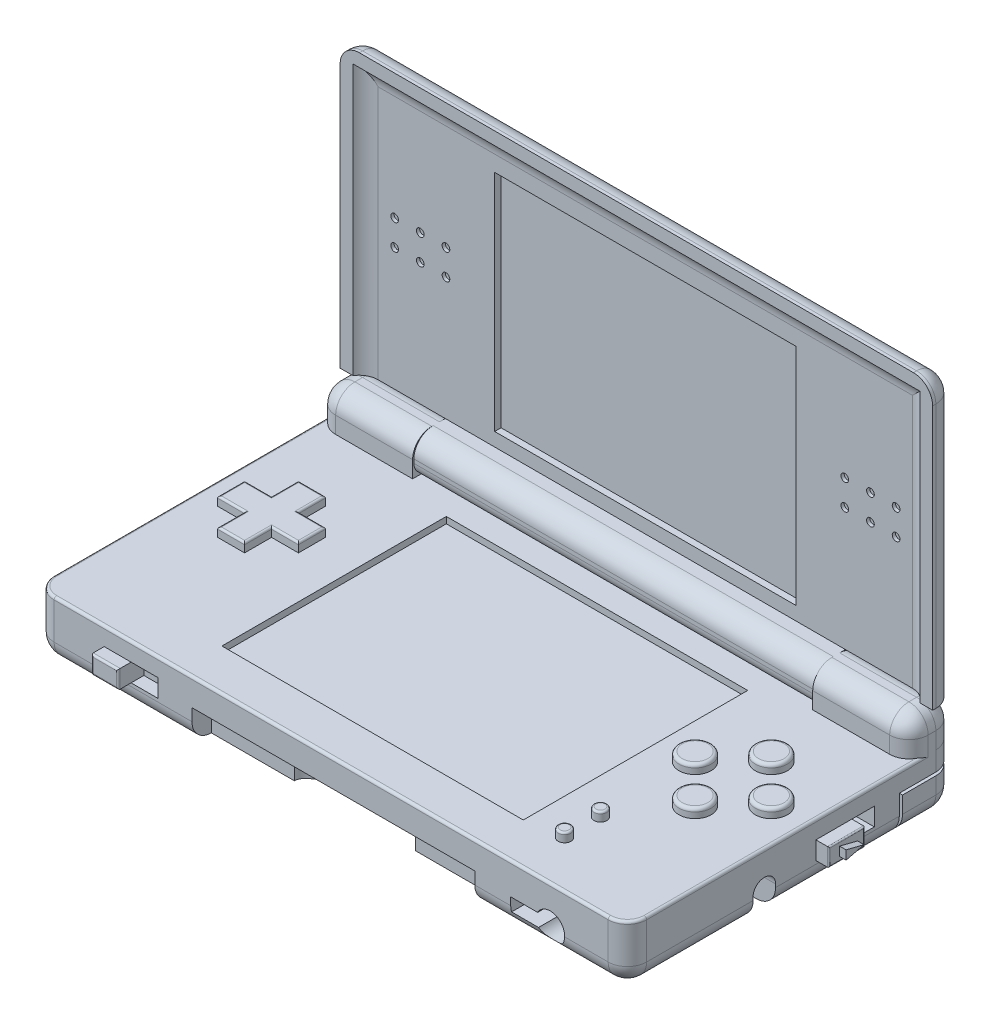
SolidWorks part; units mm, degrees
ref_plane "정면" through (0, 0, 0) normal (0, 0, 1) x (1, 0, 0)
ref_plane "윗면" through (0, 0, 0) normal (0, 1, 0) x (1, 0, 0)
ref_plane "우측면" through (0, 0, 0) normal (1, 0, 0) x (0, 0, -1)
sketch "스케치1" plane through (0, 0, 0) normal (0, 1, 0) x (1, 0, 0)
  line L0 (-46.2, 25.55) -> (46.2, -25.55) construction
  line L1 (-46.2, 25.55) -> (46.2, 25.55)
  line L2 (-46.2, 25.55) -> (-46.2, -25.55)
  line L3 (-46.2, -25.55) -> (46.2, -25.55)
  line L4 (46.2, 25.55) -> (46.2, -25.55)
  line L5 (46.2, 25.55) -> (-46.2, -25.55) construction
  dimension "D1" = 92.4
  dimension "D2" = 51.1
extrude "보스-돌출1" add sketch "스케치1" along normal blind 9.1 contours L1 L4 L3 L2
fillet "필렛1" radius 3 3 edges at (-46.2, 0, 0) (0, 0, 25.55) (-46.2, 4.55, 25.55)
fillet "필렛2" radius 3 3 edges at (46.2, 0, -1.5) (46.2, 0.8787, 24.6713) (46.2, 6.05, 25.55)
fillet "필렛3" radius 3 5 edges at (-46.2, 6.05, -25.55) (-45.3213, 0.8787, -25.55) (0, 0, -25.55) (45.3213, 0.8787, -25.55) (46.2, 6.05, -25.55)
sketch "스케치4" plane through (0, 9.1, 0) normal (0, 1, 0) x (1, 0, 0)
  line L0 (-43.2, 25.55) -> (43.2, 25.55) construction
  line L1 (31.2, 25.55) -> (46.2, 25.55)
  line L2 (31.2, 25.55) -> (31.2, 18.35)
  line L3 (31.2, 18.35) -> (46.2, 18.35)
  line L4 (46.2, 25.55) -> (46.2, 18.35)
  line L5 (46.2, 22.55) -> (46.2, -22.55) construction
  line L6 (-46.2, 22.55) -> (-46.2, -22.55) construction
  line L7 (-46.2, 25.55) -> (-31.2, 25.55)
  line L8 (-46.2, 25.55) -> (-46.2, 18.35)
  line L9 (-46.2, 18.35) -> (-31.2, 18.35)
  line L10 (-31.2, 25.55) -> (-31.2, 18.35)
  dimension "D1" = 7.2
  dimension "D2" = 15
  dimension "D3" = 7.2
  dimension "D4" = 15
extrude "보스-돌출4" add sketch "스케치4" along normal blind 5.6 contours L9 L10 L7 L8 | L3 L4 L1 L2
fillet "필렛11" radius 3 6 edges at (46.2, 14.7, -21.95) (46.2, 11.9, -25.55) (38.7, 14.7, -25.55) (-46.2, 14.7, -21.95) (-38.7, 14.7, -25.55) (-46.2, 11.9, -25.55)
fillet "필렛13" radius 3 3 edges at (-45.3213, 13.8213, -18.35) (-37.2, 14.7, -18.35)
fillet "필렛14" radius 3 3 edges at (46.2, 10.4, -18.35) (45.3213, 13.8213, -18.35) (37.2, 14.7, -18.35)
sketch "스케치10" plane through (0, 9.1, 0) normal (0, 1, 0) x (1, 0, 0)
  line L0 (-31.2, 25.55) -> (31.2, 25.55) construction
  line L1 (-31.2, 25.55) -> (31.2, 25.55)
  line L2 (-31.2, 25.55) -> (-31.2, 18.55)
  line L3 (-31.2, 18.55) -> (31.2, 18.55)
  line L4 (31.2, 25.55) -> (31.2, 18.55)
  dimension "D1" = 7
extrude "보스-돌출12" add sketch "스케치10" along normal blind 5.6 separate body contours L3 L4 L1 L2
fillet "필렛17" radius 2 1 edges at (0, 9.1, -25.55)
fillet "필렛18" radius 2 1 edges at (0, 9.1, -18.55)
fillet "필렛20" radius 3 1 edges at (0, 14.7, -18.55)
sketch "스케치12" plane through (0, 14.7, 0) normal (0, 1, 0) x (1, 0, 0)
  line L0 (-31.2, 25.55) -> (31.2, 25.55) construction
  line L1 (-46.2, 25.55) -> (46.2, 25.55)
  line L2 (-46.2, 25.55) -> (-46.2, 22.05)
  line L3 (-46.2, 22.05) -> (46.2, 22.05)
  line L4 (46.2, 25.55) -> (46.2, 22.05)
  line L5 (-46.2, 21.35) -> (-46.2, -22.55) construction
  dimension "D1" = 92.4
  dimension "D2" = 3.5
  dimension "D3" = 0
extrude "보스-돌출13" add sketch "스케치12" along normal blind 44.1
sketch "스케치13" plane through (0, 0, -22.05) normal (0, 0, 1) x (1, 0, 0)
  line L0 (-46.2, 58.8) -> (-46.2, 14.7) construction
  line L1 (-44.2, 56.8) -> (44.2, 56.8)
  line L2 (-44.2, 56.8) -> (-44.2, 14.7)
  line L3 (-44.2, 14.7) -> (44.2, 14.7)
  line L4 (44.2, 56.8) -> (44.2, 14.7)
  line L7 (-43.2, 14.7) -> (43.2, 14.7) construction
  line L9 (-46.2, 58.8) -> (46.2, 58.8) construction
  line L10 (46.2, 58.8) -> (46.2, 14.7) construction
  dimension "D1" = 2
  dimension "D2" = 2
  dimension "D3" = 2
  dimension "D4" = 0
extrude "컷-돌출3" cut sketch "스케치13" against normal blind 1.4
fillet "필렛26" radius 3 3 edges at (-44.2, 35.75, -23.45) (0, 56.8, -23.45) (44.2, 35.75, -23.45)
fillet "필렛27" radius 3 1 edges at (46.2, 58.8, -23.8)
fillet "필렛28" radius 3 1 edges at (-46.2, 58.8, -23.8)
fillet "필렛29" radius 3 5 edges at (45.3213, 57.9213, -25.55) (-46.2, 35.25, -25.55) (-45.3213, 57.9213, -25.55) (46.2, 35.25, -25.55) (0, 58.8, -25.55)
sketch "스케치14" plane through (0, 9.1, 0) normal (0, 1, 0) x (1, 0, 0)
  line L0 (-43.2, 18.35) -> (-31.2, 18.35) construction
  line L1 (-38.5, 7.85) -> (-38.5, 3.65)
  line L2 (-42.7, 3.65) -> (-42.7, -0.55)
  line L3 (-42.7, -0.55) -> (-38.5, -0.55)
  line L4 (-38.5, -0.55) -> (-38.5, -4.75)
  line L5 (-46.2, 21.35) -> (-46.2, -22.55) construction
  line L7 (-38.5, -4.75) -> (-34.3, -4.75)
  line L8 (-34.3, -4.75) -> (-34.3, -0.55)
  line L9 (-34.3, -0.55) -> (-30.1, -0.55)
  line L10 (-30.1, -0.55) -> (-30.1, 3.65)
  line L11 (-30.1, 3.65) -> (-34.3, 3.65)
  line L12 (-34.3, 3.65) -> (-34.3, 7.85)
  line L13 (-34.3, 7.85) -> (-38.5, 7.85)
  line L14 (-38.5, 3.65) -> (-42.7, 3.65)
  dimension "D1" = 4.2
  dimension "D2" = 4.2
  dimension "D3" = 4.2
  dimension "D4" = 4.2
  dimension "D5" = 10.5
  dimension "D6" = 3.5
  dimension "D7" = 4.2
  dimension "D8" = 4.2
extrude "보스-돌출14" add sketch "스케치14" along normal blind 1.4
sketch "스케치15" plane through (0, 9.1, 0) normal (0, 1, 0) x (1, 0, 0)
  line L0 (29, 2.2) -> (40.9, 2.2) construction
  line L1 (34.95, 8.15) -> (34.95, -3.75) construction
  line L2 (46.2, 21.35) -> (46.2, -22.55) construction
  line L3 (31.2, 18.35) -> (43.2, 18.35) construction
  circle A0 centre (34.95, 8.15) radius 2.5
  circle A1 centre (29, 2.2) radius 2.5
  circle A2 centre (34.95, -3.75) radius 2.5
  circle A3 centre (40.9, 2.2) radius 2.5
  point P8 (34.95, 2.2)
  point P9 (34.95, 2.2)
  point P10 (34.95, 10.65)
  point P13 (43.4, 2.2)
  dimension "D1" = 5
  dimension "D5" = 11.9
  dimension "D6" = 11.9
  dimension "D7" = 7.7
  dimension "D2" = 5
  dimension "D3" = 5
  dimension "D4" = 5
  dimension "D8" = 2.8
extrude "보스-돌출15" add sketch "스케치15" along normal blind 1.4 contours A0 | A1 | A3 | A2
sketch "스케치16" plane through (0, 9.1, 0) normal (0, 1, 0) x (1, 0, 0)
  line L0 (-43.2, -25.55) -> (43.2, -25.55) construction
  line L1 (46.2, 21.35) -> (46.2, -22.55) construction
  circle A0 centre (29.1, -12.65) radius 1
  circle A1 centre (29.1, -18.25) radius 1
  point P4 (29.1, -19.25)
  point P7 (30.1, -18.25)
  dimension "D1" = 2
  dimension "D5" = 2
  dimension "D2" = 6.3
  dimension "D3" = 16.1
  dimension "D4" = 5.6
extrude "보스-돌출16" add sketch "스케치16" along normal blind 1.4
sketch "스케치17" plane through (0, 0, -23.45) normal (0, 0, 1) x (1, 0, 0)
  line L0 (-46.2, 55.8) -> (-46.2, 14.7) construction
  line L5 (41.6623, 54.2623) -> (-41.6623, 54.2623) construction
  line L6 (0, 68.9396) -> (0, -17.3507) construction
  circle A0 centre (39.1, 33.8515) radius 0.6
  circle A1 centre (35.1, 33.8515) radius 0.6
  circle A2 centre (31.1, 33.8515) radius 0.6
  circle A3 centre (31.1, 37.8515) radius 0.6
  circle A4 centre (35.1, 37.8515) radius 0.6
  circle A5 centre (39.1, 37.8515) radius 0.6
  circle A7 centre (-39.1, 33.8515) radius 0.6
  circle A8 centre (-35.1, 33.8515) radius 0.6
  circle A9 centre (-31.1, 33.8515) radius 0.6
  circle A10 centre (-39.1, 37.8515) radius 0.6
  circle A11 centre (-35.1, 37.8515) radius 0.6
  circle A12 centre (-31.1, 37.8515) radius 0.6
  point P0 (-38.5, 37.8515)
  point P27 (-35.7, 37.8515)
  point P28 (-34.5, 37.8515)
  point P29 (-31.7, 37.8515)
  point P30 (-31.1, 34.4515)
  point P31 (-31.1, 37.2515)
  point P32 (-35.1, 37.2515)
  point P33 (-35.1, 34.4515)
  point P34 (-34.5, 33.8515)
  point P35 (-35.7, 33.8515)
  point P36 (-38.5, 33.8515)
  point P37 (-31.7, 33.8515)
  point P38 (-39.1, 34.4515)
  dimension "D1" = 7.7
  dimension "D5" = 1.2
  dimension "D6" = 16.4108
  dimension "D2" = 2.8
  dimension "D3" = 2.8
  dimension "D4" = 2.8
  dimension "D11" = 2.8
  dimension "D12" = 2.8
extrude "컷-돌출4" cut sketch "스케치17" against normal blind 0.5 contours A10 | A11 | A12 | A8 | A7 | A9 | A3 | A2 | A1 | A0 | A5 | A4
sketch "스케치20" plane through (0, 0, -25.55) normal (0, 0, -1) x (-1, 0, 0)
  line L1 (43.2, 0) -> (-43.2, 0) construction
  line L2 (-22.4, 4.9) -> (-20.3, 4.9)
  line L3 (-22.4, 4.9) -> (-22.4, 3.5)
  line L4 (-22.4, 3.5) -> (-20.3, 3.5)
  line L6 (-20.3, 4.9) -> (-20.3, 3.5)
  line L7 (-46.2, 3) -> (-46.2, 9.1) construction
  line L8 (-18.2, 4.9) -> (-16.1, 4.9)
  line L9 (-18.2, 4.9) -> (-18.2, 3.5)
  line L10 (-18.2, 3.5) -> (-16.1, 3.5)
  line L11 (-16.1, 4.9) -> (-16.1, 3.5)
  line L12 (-19.25, 7.9937) -> (-19.25, 0.4019) construction
  dimension "D1" = 3.5
  dimension "D2" = 1.4
  dimension "D3" = 2.1
  dimension "D4" = 23.8
  dimension "D5" = 1.4
  dimension "D6" = 2.1
  dimension "D7" = 3.5
  dimension "D8" = 2.1
  dimension "D9" = 1.05
revolve "컷-회전2" cut sketch "스케치20" angle 360 about L12
sketch "스케치22" plane through (0, 0, -25.55) normal (0, 0, -1) x (-1, 0, 0)
  line L0 (43.2, 0) -> (-43.2, 0) construction
  line L1 (-12.6, 4.9) -> (11.2, 4.9)
  line L2 (-12.6, 4.9) -> (-12.6, 1.4)
  line L3 (-12.6, 1.4) -> (11.2, 1.4)
  line L4 (11.2, 4.9) -> (11.2, 1.4)
  line L5 (-16.1, 3.5) -> (-16.1, 4.9) construction
  point P6 (-16.1, 4.2)
  dimension "D1" = 23.8
  dimension "D2" = 3.5
  dimension "D3" = 1.4
  dimension "D4" = 3.5
extrude "컷-돌출7" cut sketch "스케치22" against normal blind 18.9
sketch "스케치23" plane through (0, 0, -25.55) normal (0, 0, -1) x (-1, 0, 0)
  line L0 (43.2, 0) -> (-43.2, 0) construction
  line L2 (14.7, 5.6) -> (14.7, 3.5)
  line L3 (14.7, 3.5) -> (21, 3.5)
  line L4 (21, 5.6) -> (21, 3.5)
  line L5 (14.7, 5.6) -> (15.6899, 6.5899)
  line L6 (15.6899, 6.5899) -> (20.0101, 6.5899)
  line L7 (20.0101, 6.5899) -> (21, 5.6)
  dimension "D1" = 3.5
  dimension "D2" = 2.1
  dimension "D3" = 3.5
  dimension "D4" = 6.3
  dimension "D5" = 1.4
  dimension "D6" = 1.4
  dimension "D7" = 135
  dimension "D8" = 135
extrude "컷-돌출9" cut sketch "스케치23" against normal blind 10
sketch "스케치25" plane through (46.2, 0, 0) normal (1, 0, 0) x (0, 0, -1)
  line L0 (-5.95, 0) -> (-5.95, 3.5)
  line L1 (22.55, 0) -> (-22.55, 0) construction
  line L2 (-2.45, 0) -> (-2.45, 3.5)
  line L3 (-25.55, 3) -> (-25.55, 9.1) construction
  line L4 (-5.95, 0) -> (-2.45, 0)
  arc A0 (-5.95, 3.5) -> (-2.45, 3.5) centre (-4.2, 3.5) cw
  dimension "D3" = 1.75
  dimension "D1" = 19.6
  dimension "D2" = 3.5
  dimension "D4" = 3.5
extrude "컷-돌출10" cut sketch "스케치25" against normal blind 7
sketch "스케치26" plane through (39.2, 0, 0) normal (1, 0, 0) x (0, 0, -1)
  line L0 (-5.95, 0.246) -> (-2.45, 0.246)
  line L1 (-5.95, 3.5) -> (-5.95, 0) construction
  line L2 (-2.45, 0) -> (-2.45, 3.5) construction
  line L3 (-5.95, 3.5) -> (-5.95, 0.246)
  line L4 (-2.45, 3.5) -> (-2.45, 0.246)
  line L7 (-5.95, 0) -> (-2.45, 0) construction
  arc A0 (-2.45, 3.5) -> (-5.95, 3.5) centre (-4.2, 3.5) ccw
  dimension "D1" = 1.75
  dimension "D2" = 0.246
  dimension "D3" = 3.254
extrude "컷-돌출11" cut sketch "스케치26" against normal blind 53.9
sketch "스케치27" plane through (46.2, 0, 0) normal (1, 0, 0) x (0, 0, -1)
  line L0 (25.55, 9.1) -> (25.55, 3) construction
  line L1 (3.85, 6.3) -> (12.95, 6.3)
  line L2 (3.85, 6.3) -> (3.85, 3.5)
  line L3 (3.85, 3.5) -> (12.95, 3.5)
  line L4 (12.95, 6.3) -> (12.95, 3.5)
  line L5 (21.35, 9.1) -> (-22.55, 9.1) construction
  dimension "D1" = 9.1
  dimension "D2" = 2.8
  dimension "D3" = 12.6
  dimension "D4" = 2.8
extrude "컷-돌출12" cut sketch "스케치27" against normal blind 5
sketch "스케치28" plane through (41.2, 0, 0) normal (1, 0, 0) x (0, 0, -1)
  line L0 (12.95, 6.3) -> (3.85, 6.3) construction
  line L1 (3.85, 3.5) -> (9.45, 3.5)
  line L2 (3.85, 3.5) -> (3.85, 6.3)
  line L3 (3.85, 6.3) -> (9.45, 6.3)
  line L4 (9.45, 3.5) -> (9.45, 6.3)
  line L5 (3.85, 6.3) -> (3.85, 3.5) construction
  line L6 (3.85, 3.5) -> (12.95, 3.5) construction
  dimension "D1" = 5.6
  dimension "D2" = 0
  dimension "D3" = 0
  dimension "D4" = 0
extrude "보스-돌출17" add sketch "스케치28" along normal blind 7
sketch "스케치29" plane through (48.2, 0, 0) normal (1, 0, 0) x (0, 0, -1)
  line L0 (5.55, 5.6) -> (5.55, 4.2)
  line L1 (5.55, 4.2) -> (8.35, 4.9)
  line L2 (8.35, 4.9) -> (5.55, 5.6)
  line L3 (3.85, 6.3) -> (3.85, 3.5) construction
  line L4 (5.55, 4.9) -> (10.966, 4.9) construction
  line L5 (3.85, 3.5) -> (9.45, 3.5) construction
  point P4 (8.35, 4.9)
  dimension "D1" = 1.4
  dimension "D2" = 2.8
  dimension "D3" = 1.7
  dimension "D4" = 0.7
extrude "보스-돌출19" add sketch "스케치29" along normal blind 1
sketch "스케치32" plane through (0, 0, -23.45) normal (0, 0, 1) x (1, 0, 0)
  line L1 (-24.5023, 52.8) -> (24.4977, 52.8)
  line L2 (-24.5023, 52.8) -> (-24.5023, 15.8)
  line L3 (-24.5023, 15.8) -> (24.4977, 15.8)
  line L4 (24.4977, 52.8) -> (24.4977, 15.8)
  line L7 (-43.2, 58.8) -> (43.2, 58.8) construction
  line L13 (-41.6623, 54.2623) -> (-41.6623, 14.7) construction
  line L16 (-23.5023, 51.8) -> (23.4977, 51.8)
  line L17 (-23.5023, 51.8) -> (-23.5023, 16.8)
  line L18 (-23.5023, 16.8) -> (23.4977, 16.8)
  line L19 (23.4977, 51.8) -> (23.4977, 16.8)
  dimension "D1" = 49
  dimension "D2" = 37
  dimension "D3" = 6
  dimension "D4" = 17.16
  dimension "D5" = 1
  dimension "D6" = 1
  dimension "D7" = 1
  dimension "D8" = 1
fillet "필렛32" radius 0.5 1 edges at (40.9, 10.5, 0.3)
fillet "필렛33" radius 0.5 3 edges at (34.95, 10.5, -5.65) (29, 10.5, 0.3) (34.95, 10.5, 6.25)
fillet "필렛34" radius 0.3 2 edges at (29.1, 10.5, 13.65) (29.1, 10.5, 19.25)
fillet "필렛35" radius 0.3 12 edges at (-34.3, 10.5, -5.75) (-32.2, 10.5, -3.65) (-30.1, 10.5, -1.55) (-32.2, 10.5, 0.55) (-34.3, 10.5, 2.65) (-36.4, 10.5, 4.75) (-38.5, 10.5, 2.65) (-40.6, 10.5, 0.55) (-42.7, 10.5, -1.55) (-40.6, 10.5, -3.65) (-38.5, 10.5, -5.75) (-36.4, 10.5, -7.85)
fillet "필렛36" radius 0.4 5 edges at (-45.3213, 9.1, 24.6713) (45.3213, 9.1, 24.6713) (46.2, 9.1, 0.6) (0, 9.1, 25.55)
fillet "필렛37" radius 0.2 4 edges at (48.2, 4.9, -3.85) (48.2, 3.5, -6.65) (48.2, 4.9, -9.45) (48.2, 6.3, -6.65)
sketch "스케치33" plane through (0, 0, -23.45) normal (0, 0, 1) x (1, 0, 0)
sketch "스케치34" plane through (0, 0, 25.55) normal (0, 0, 1) x (1, 0, 0)
  line L0 (-46.2, 3) -> (-46.2, 8.7) construction
  line L1 (-35.4, 6.3) -> (-27, 6.3)
  line L2 (-35.4, 6.3) -> (-35.4, 3.5)
  line L3 (-35.4, 3.5) -> (-27, 3.5)
  line L4 (-27, 6.3) -> (-27, 3.5)
  line L6 (-34.3, 9.1) -> (-30.1, 9.1) construction
  line L7 (43.2, 0) -> (-43.2, 0) construction
  point P4 (-46.2, 5.85)
  dimension "D1" = 10.8
  dimension "D2" = 8.4
  dimension "D3" = 2.8
  dimension "D4" = 3.5
extrude "컷-돌출14" cut sketch "스케치34" against normal blind 2
sketch "스케치35" plane through (0, 0, 23.55) normal (0, 0, 1) x (1, 0, 0)
  line L0 (-27, 6.3) -> (-35.4, 6.3) construction
  line L1 (-31.2, 6.3) -> (-35.4, 6.3)
  line L2 (-31.2, 6.3) -> (-31.2, 3.5)
  line L3 (-31.2, 3.5) -> (-35.4, 3.5)
  line L4 (-35.4, 6.3) -> (-35.4, 3.5)
  dimension "D1" = 4.2
extrude "보스-돌출20" add sketch "스케치35" along normal blind 4
fillet "필렛38" radius 0.3 4 edges at (-31.2, 4.9, 27.55) (-33.3, 3.5, 27.55) (-35.4, 4.9, 27.55) (-33.3, 6.3, 27.55)
sketch "스케치36" plane through (0, 0, 25.55) normal (0, 0, 1) x (1, 0, 0)
  line L0 (43.2, 0) -> (-43.2, 0) construction
  line L1 (28, 4.2) -> (32.2, 4.2)
  line L2 (28, 4.2) -> (28, 2.1)
  line L3 (28, 2.1) -> (32.2, 2.1)
  line L4 (32.2, 4.2) -> (32.2, 2.1)
  line L5 (46.2, 3.5) -> (46.2, 3) construction
  circle A0 centre (34.1687, 3.15) radius 2.2312
  point P8 (36.4, 3.15)
  point P9 (46.2, 3.25)
  line M10 (-43.2, 3) -> (43.2, 3)
  dimension "D1" = 2.1
  dimension "D6" = 4.4625
  dimension "D2" = 4.2
  dimension "D3" = 2.1
  dimension "D4" = 8.4
  dimension "D5" = 9.8
extrude "컷-돌출17" cut sketch "스케치36" against normal blind 4 contours A0 L4 M10 | L4 A0 M10 | A0 L1 L2 M10 | A0 L2 L3 M10
sketch "스케치38" plane through (0, 0, 21.55) normal (0, 0, 1) x (1, 0, 0)
  circle A0 centre (34.1687, 3.15) radius 2.23
  arc A1 (32.2, 2.1) -> (32.2, 4.2) centre (34.1687, 3.15) ccw construction
  dimension "D1" = 4.46
extrude "컷-돌출19" cut sketch "스케치38" against normal blind 7
sketch "스케치39" plane through (0, 0, 0) normal (0, -1, 0) x (1, 0, 0)
  line L0 (-8.75, 22.55) -> (10.15, 22.55)
  line L3 (46.2, 22.55) -> (46.2, 5.95) construction
  line L4 (43.2, 22.55) -> (-43.2, 22.55) construction
  ellipse E0 centre (0.7, 22.55) end of major axis (-8.75, 22.55) minor radius 3.5 (10.15, 22.55) -> (-8.75, 22.55) cw
  dimension "D1" = 18.9
  dimension "D2" = 3.5
  dimension "D4" = 45.5
extrude "컷-돌출20" cut sketch "스케치39" against normal blind 5.6
sketch "스케치40" plane through (0, 0, 25.55) normal (0, 0, 1) x (1, 0, 0)
  line L0 (-8.75, 0) -> (-43.2, 0) construction
  line L1 (-21.7, 4.9) -> (22.4, 4.9)
  line L2 (-21.7, 4.9) -> (-21.7, 0)
  line L3 (-21.7, 0) -> (22.4, 0)
  line L4 (22.4, 4.9) -> (22.4, 0)
  line L5 (-46.2, 3) -> (-46.2, 8.7) construction
  dimension "D1" = 44.1
  dimension "D2" = 4.9
  dimension "D3" = 0
  dimension "D4" = 24.5
extrude "컷-돌출23" cut sketch "스케치40" against normal blind 16.8
sketch "스케치41" plane through (0, 4.9, 0) normal (0, -1, 0) x (1, 0, 0)
  line L0 (-21.7, 22.55) -> (-21.7, 8.75)
  line L1 (-21.7, 8.75) -> (22.4, 8.75)
  line L2 (22.4, 8.75) -> (22.4, 22.55)
  line L3 (22.4, 8.75) -> (22.4, 25.55) construction
  line L4 (22.4, 22.55) -> (10.15, 22.55)
  line L5 (-21.7, 22.55) -> (-8.75, 22.55)
  line L7 (10.15, 22.55) -> (-8.75, 22.55)
  ellipse E1 centre (0.7, 22.55) end of major axis (-8.75, 22.55) minor radius 3.5 (-8.75, 22.55) -> (10.15, 22.55) ccw
  ellipse E2 centre (0.7, 22.55) end of major axis (-8.75, 22.55) minor radius 3.5 (-8.75, 22.55) -> (10.15, 22.55) ccw
  dimension "D1" = 0
extrude "보스-돌출21" add sketch "스케치41" along normal blind 4.9
sketch "스케치42" plane through (0, 0, -25.55) normal (0, 0, -1) x (-1, 0, 0)
  line L0 (43.2, 0) -> (-43.2, 0) construction
  line L1 (31.7, 5.6) -> (32.2, 5.6)
  line L2 (31.7, 5.6) -> (31.7, 0)
  line L3 (31.7, 0) -> (32.2, 0)
  line L4 (32.2, 5.6) -> (32.2, 0)
  line L5 (46.2, 9.1) -> (46.2, 3) construction
  line L7 (31.7, 6.1) -> (46.2, 6.1)
  line L8 (31.7, 6.1) -> (31.7, 5.6)
  line L9 (31.7, 5.6) -> (46.2, 5.6)
  line L10 (46.2, 6.1) -> (46.2, 5.6)
  dimension "D1" = 0.5
  dimension "D2" = 0
  dimension "D3" = 14
  dimension "D4" = 5.6
  dimension "D5" = 0.5
  dimension "D6" = 0
  dimension "D7" = 0
extrude "컷-돌출27" cut sketch "스케치42" against normal blind 1 contours L7 L10 L9 L8 | L2 L3 L4 L1
sketch "스케치46" plane through (-46.2, 0, 0) normal (-1, 0, 0) x (0, 0, 1)
  line L1 (-24.55, 6.1) -> (-17.35, 6.1)
  line L2 (-24.55, 6.1) -> (-24.55, 5.6)
  line L3 (-24.55, 5.6) -> (-17.35, 5.6)
  line L4 (-17.35, 6.1) -> (-17.35, 5.6)
  line L5 (-17.35, 6.1) -> (-16.85, 6.1)
  line L6 (-17.35, 6.1) -> (-17.35, 0)
  line L7 (-17.35, 0) -> (-16.85, 0)
  line L8 (-16.85, 6.1) -> (-16.85, 0)
  dimension "D1" = 0.5
  dimension "D2" = 7.2
  dimension "D3" = 0
  dimension "D4" = 0
  dimension "D5" = 0.5
  dimension "D6" = 0
  dimension "D7" = 0
extrude "컷-돌출28" cut sketch "스케치46" against normal blind 1 contours L1 L4 L3 L2 | L5 L8 L7 L6
sketch "스케치47" plane through (0, 0, 0) normal (0, -1, 0) x (1, 0, 0)
  line L0 (-32.2, -25.55) -> (-32.2, -24.55) construction
  line L1 (-45.2, -16.85) -> (-32.2, -16.85)
  line L2 (-45.2, -16.85) -> (-45.2, -17.35)
  line L3 (-45.2, -17.35) -> (-32.2, -17.35)
  line L4 (-32.2, -16.85) -> (-32.2, -17.35)
  line L6 (-32.2, -16.85) -> (-31.7, -16.85)
  line L7 (-32.2, -16.85) -> (-32.2, -25.55)
  line L8 (-32.2, -25.55) -> (-31.7, -25.55)
  line L9 (-31.7, -16.85) -> (-31.7, -25.55)
  dimension "D1" = 0.5
  dimension "D2" = 0
  dimension "D3" = 0
  dimension "D4" = 0
extrude "컷-돌출30" cut sketch "스케치47" against normal blind 1 contours L4 L3 L2 L1 | L7 L8 L9 L6
sketch "스케치48" plane through (0, 0, -25.55) normal (0, 0, -1) x (-1, 0, 0)
  line L0 (-46.2, 3) -> (-46.2, 9.1) construction
  line L1 (-46.2, 6.1) -> (-32.2, 6.1)
  line L2 (-46.2, 6.1) -> (-46.2, 5.6)
  line L3 (-46.2, 5.6) -> (-32.2, 5.6)
  line L4 (-32.2, 6.1) -> (-32.2, 5.6)
  line L5 (31.7, 0) -> (-43.2, 0) construction
  line L7 (-32.2, 6.1) -> (-31.7, 6.1)
  line L8 (-32.2, 6.1) -> (-32.2, 0)
  line L9 (-32.2, 0) -> (-31.7, 0)
  line L10 (-31.7, 6.1) -> (-31.7, 0)
  dimension "D1" = 0.5
  dimension "D2" = 0
  dimension "D3" = 14
  dimension "D4" = 5.6
  dimension "D5" = 0.5
extrude "컷-돌출32" cut sketch "스케치48" against normal blind 1 contours L4 L3 L2 L1 | L8 L9 L10 L7
sketch "스케치51" plane through (46.2, 0, 0) normal (1, 0, 0) x (0, 0, -1)
  line L0 (24.55, 6.1) -> (24.55, 5.6) construction
  line L1 (17.35, 5.6) -> (24.55, 5.6)
  line L2 (17.35, 5.6) -> (17.35, 6.1)
  line L3 (17.35, 6.1) -> (24.55, 6.1)
  line L4 (24.55, 5.6) -> (24.55, 6.1)
  line L5 (25.55, 9.1) -> (25.55, 6.1) construction
  line L6 (22.55, 0) -> (-2.45, 0) construction
  line L7 (17.35, 6.1) -> (16.85, 6.1)
  line L8 (17.35, 6.1) -> (17.35, 0)
  line L9 (17.35, 0) -> (16.85, 0)
  line L10 (16.85, 6.1) -> (16.85, 0)
  dimension "D1" = 0.5
  dimension "D2" = 0
  dimension "D3" = 0
  dimension "D4" = 8.2
  dimension "D5" = 0.5
  dimension "D6" = 0
extrude "컷-돌출35" cut sketch "스케치51" against normal blind 1 contours L7 L10 L9 L8 | L3 L4 L1 L2
sketch "스케치53" plane through (0, 0, 0) normal (0, -1, 0) x (1, 0, 0)
  line L1 (31.7, -24.55) -> (32.2, -24.55)
  line L2 (31.7, -24.55) -> (31.7, -16.85)
  line L3 (31.7, -16.85) -> (32.2, -16.85)
  line L4 (32.2, -24.55) -> (32.2, -16.85)
  line L5 (45.2, -17.35) -> (32.2, -17.35)
  line L6 (45.2, -17.35) -> (45.2, -16.85)
  line L7 (45.2, -16.85) -> (32.2, -16.85)
  line L8 (32.2, -17.35) -> (32.2, -16.85)
  dimension "D1" = 0.5
  dimension "D2" = 7.7
extrude "컷-돌출36" cut sketch "스케치53" against normal blind 1 contours L7 L6 L5 L8 | L4 L1 L2 L3
sketch "스케치59" plane through (0, 0, -23.45) normal (0, 0, 1) x (1, 0, 0)
  point P13 (-12.6129, 77.1835)
  point P14 (-5.9295, 72.3446)
extrude "컷-돌출37" cut sketch "스케치32" against normal blind 1 contours L16 L19 L18 L17
sketch "스케치60" plane through (0, 9.1, 0) normal (0, 1, 0) x (1, 0, 0)
  line L1 (-46.2, -22.55) -> (-46.2, 21.35) construction
  line L2 (-23.5, 15.9073) -> (23.5, 15.9073)
  line L3 (-23.5, 15.9073) -> (-23.5, -19.0927)
  line L4 (-23.5, -19.0927) -> (23.5, -19.0927)
  line L5 (23.5, 15.9073) -> (23.5, -19.0927)
  line L8 (-43.2, -25.15) -> (43.2, -25.15) construction
  dimension "D1" = 47
  dimension "D2" = 35
  dimension "D3" = 22.7
  dimension "D4" = 6.0573
extrude "컷-돌출39" cut sketch "스케치60" against normal blind 1
sketch "스케치61" plane through (0, 0, -25.55) normal (0, 0, -1) x (-1, 0, 0)
  text T0 "R"
extrude "컷-돌출40" cut sketch "스케치61" against normal blind 1
sketch "스케치63" plane through (0, 0, -25.55) normal (0, 0, -1) x (-1, 0, 0)
  text T0 "L"
extrude "컷-돌출41" cut sketch "스케치63" against normal blind 1
sketch "스케치64" plane through (0, 0, 0) normal (0, -1, 0) x (-1, 0, 0)
  text T0 "고명훈\r\n박성진\r\n박지현\r\n임우섭"
extrude "컷-돌출42" cut sketch "스케치64" against normal blind 1
